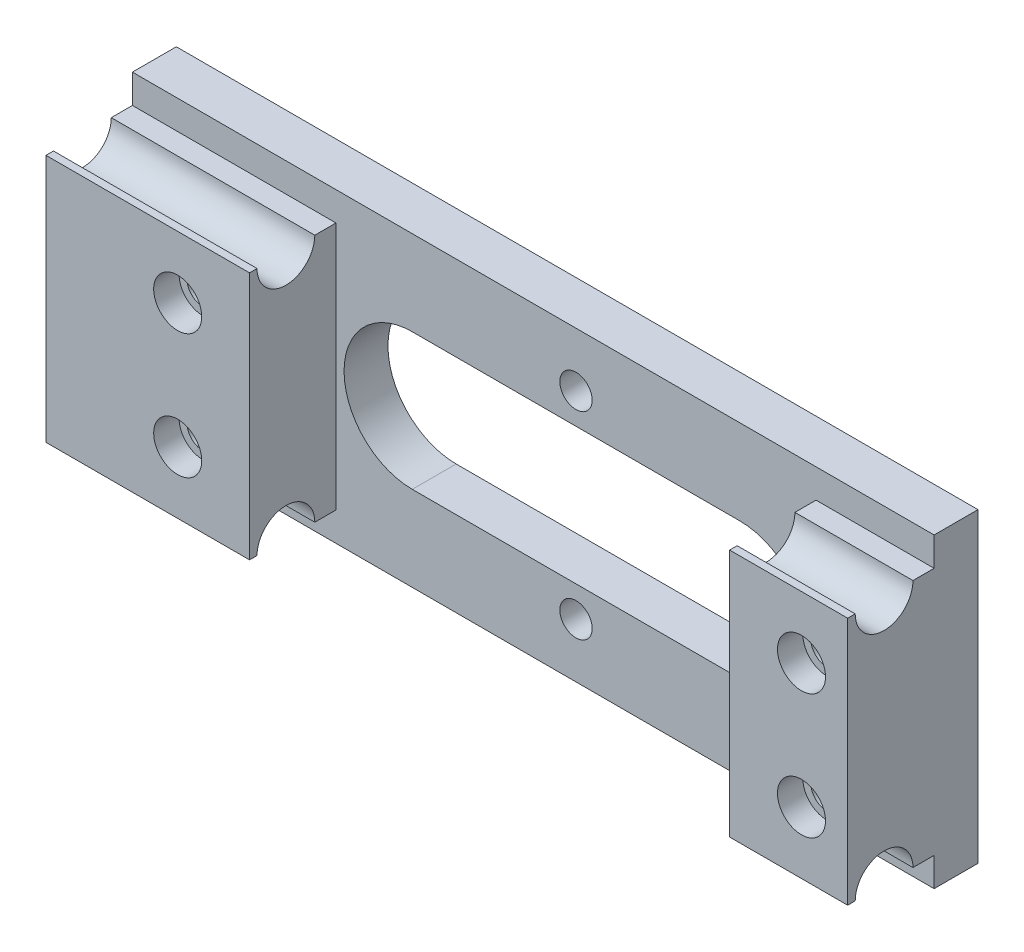
SolidWorks part; units mm, degrees
ref_plane "Front Plane" through (0, 0, 0) normal (0, 0, 1) x (1, 0, 0)
ref_plane "Top Plane" through (0, 0, 0) normal (0, 1, 0) x (1, 0, 0)
ref_plane "Right Plane" through (0, 0, 0) normal (1, 0, 0) x (0, 0, -1)
sketch "Sketch1" plane through (0, 0, 0) normal (0, 0, 1) x (1, 0, 0)
  line L1 (-22.0345, -8.4201) -> (22.0345, -8.4201)
  line L2 (-22.0345, -8.4201) -> (-22.0345, 8.4201)
  line L3 (-22.0345, 8.4201) -> (22.0345, 8.4201)
  line L4 (22.0345, -8.4201) -> (22.0345, 8.4201)
  line L5 (-22.0345, -8.4201) -> (22.0345, 8.4201) construction
  line L6 (-22.0345, 8.4201) -> (22.0345, -8.4201) construction
  point P0 (0, 0)
  dimension "D1" = 44.069
  dimension "D2" = 16.8402
extrude "Boss-Extrude1" add sketch "Sketch1" along normal blind 7.1628
sketch "Sketch2" plane through (0, 0, 7.1628) normal (0, 0, 1) x (1, 0, 0)
  line L0 (-22.0345, 0) -> (22.0345, 0) construction
  line L1 (-10.8458, 8.4201) -> (15.5448, 8.4201)
  line L2 (-10.8458, 8.4201) -> (-10.8458, -8.4201)
  line L3 (-10.8458, -8.4201) -> (15.5448, -8.4201)
  line L4 (15.5448, 8.4201) -> (15.5448, -8.4201)
  line L5 (-22.0345, 8.4201) -> (-22.0345, -8.4201) construction
  line L6 (22.0345, -8.4201) -> (22.0345, 8.4201) construction
  line L7 (-10.8458, 8.4201) -> (-22.0345, 0) construction
  line L8 (-22.0345, 0) -> (-10.8458, -8.4201) construction
  line L9 (2.3495, 8.4201) -> (2.3495, -8.4201) construction
  line L12 (22.0345, 8.4201) -> (-22.0345, 8.4201) construction
  dimension "D1" = 26.3906
  dimension "D2" = 24.384
extrude "Cut-Extrude1" cut sketch "Sketch2" against normal blind 4.75
sketch "Sketch4" plane through (0, 0, 7.1628) normal (0, 0, 1) x (1, 0, 0)
  line L0 (-10.8458, 8.4201) -> (-10.8458, -8.4201) construction
  line L1 (-22.0345, -8.4201) -> (-10.8458, -8.4201)
  line L2 (-22.0345, -8.4201) -> (-22.0345, -6.8326)
  line L3 (-22.0345, -6.8326) -> (-10.8458, -6.8326)
  line L4 (-10.8458, -8.4201) -> (-10.8458, -6.8326)
  line L5 (-22.0345, 0) -> (-10.8458, 0) construction
  line L6 (-22.0345, 8.4201) -> (-22.0345, -8.4201) construction
  line L7 (-10.8458, 8.4201) -> (-10.8458, -8.4201) construction
  line L8 (-10.8458, 8.4201) -> (-10.8458, 6.8326)
  line L9 (-22.0345, 6.8326) -> (-10.8458, 6.8326)
  line L10 (-22.0345, 8.4201) -> (-22.0345, 6.8326)
  line L11 (-22.0345, 8.4201) -> (-10.8458, 8.4201)
  line L12 (22.0345, -8.4201) -> (22.0345, 8.4201) construction
  line L13 (15.5448, -8.4201) -> (22.0345, -8.4201)
  line L14 (15.5448, -8.4201) -> (15.5448, -6.8326)
  line L15 (15.5448, -6.8326) -> (22.0345, -6.8326)
  line L16 (22.0345, -8.4201) -> (22.0345, -6.8326)
  line L17 (15.5448, 6.8326) -> (22.0345, 6.8326)
  line L18 (22.0345, 8.4201) -> (22.0345, 6.8326)
  line L19 (15.5448, 8.4201) -> (22.0345, 8.4201)
  line L20 (15.5448, 8.4201) -> (15.5448, 6.8326)
  dimension "D1" = 1.5875
extrude "Cut-Extrude9" cut sketch "Sketch4" against normal up to surface (4.75 mm away) up to face at (2.3495, 0, 2.4128)
sketch "Sketch5" plane through (-22.0345, 0, 0) normal (-1, 0, 0) x (0, 0, 1)
  line L1 (0, 0) -> (7.1628, 0) construction
  line L2 (0, 8.4201) -> (0, -8.4201) construction
  line L3 (7.1628, 6.8326) -> (7.1628, -6.8326) construction
  circle A0 centre (5.1628, -6.8326) radius 1.5875
  circle A1 centre (5.1628, 6.8326) radius 1.5875
  dimension "D1" = 3.175
  dimension "D2" = 2
extrude "Cut-Extrude10" cut sketch "Sketch5" against normal through all
sketch "Sketch6" plane through (0, 0, 7.1628) normal (0, 0, 1) x (1, 0, 0)
  line L0 (-22.0345, 0) -> (-10.8458, 0) construction
  line L1 (-22.0345, 6.8326) -> (-22.0345, -6.8326) construction
  line L2 (-10.8458, 6.8326) -> (-10.8458, -6.8326) construction
  circle A0 centre (-14.7955, 3.429) radius 0.889
  circle A1 centre (-14.7955, -3.429) radius 0.889
  circle A2 centre (19.4945, 3.429) radius 0.889
  circle A3 centre (19.4945, -3.429) radius 0.889
  dimension "D1" = 1.778
  dimension "D2" = 6.858
  dimension "D3" = 7.239
  dimension "D4" = 2
extrude "Cut-Extrude11" cut sketch "Sketch6" against normal through all
sketch "Sketch7" plane through (0, 0, 7.1628) normal (0, 0, 1) x (1, 0, 0)
  line L0 (-22.0345, 0) -> (-10.8458, 0) construction
  line L1 (-22.0345, 6.8326) -> (-22.0345, -6.8326) construction
  line L2 (-10.8458, 6.8326) -> (-10.8458, -6.8326) construction
  circle A0 centre (-14.7955, 3.429) radius 1.3208
  circle A1 centre (-14.7955, -3.429) radius 1.3208
  circle A2 centre (19.4945, 3.429) radius 1.3208
  circle A3 centre (19.4945, -3.429) radius 1.3208
  dimension "D1" = 2.6416
  dimension "D2" = 2
extrude "Cut-Extrude12" cut sketch "Sketch7" against normal blind 1.397
sketch "Sketch9" plane through (0, 0, 0) normal (0, 0, -1) x (-1, 0, 0)
  line L0 (22.0345, 8.4201) -> (22.0345, -8.4201) construction
  line L1 (-22.0345, 0) -> (22.0345, 0) construction
  line L2 (-22.0345, -8.4201) -> (-22.0345, 8.4201) construction
  circle A0 centre (-2.3495, 5.4356) radius 0.889
  circle A1 centre (-2.3495, -5.4356) radius 0.889
  dimension "D1" = 1.778
  dimension "D2" = 24.384
  dimension "D3" = 10.8712
extrude "Cut-Extrude13" cut sketch "Sketch9" against normal through all
sketch "Sketch10" plane through (0, 0, 0) normal (0, 0, -1) x (-1, 0, 0)
  line L0 (-22.0345, 0) -> (22.0345, 0) construction
  line L1 (-22.0345, -8.4201) -> (-22.0345, 8.4201) construction
  line L2 (22.0345, 8.4201) -> (22.0345, -8.4201) construction
  circle A0 centre (-2.3495, 5.4356) radius 1.1906
  circle A1 centre (-2.3495, -5.4356) radius 1.1906
  dimension "D1" = 2.3813
extrude "Cut-Extrude14" cut sketch "Sketch10" against normal blind 1
sketch "Sketch11" plane through (0, 0, 0) normal (0, 0, -1) x (-1, 0, 0)
  line L0 (-22.0345, 0) -> (22.0345, 0) construction
  line L1 (-22.0345, -8.4201) -> (-22.0345, 8.4201) construction
  line L2 (22.0345, 8.4201) -> (22.0345, -8.4201) construction
  line L3 (-2.3495, 5.4356) -> (-2.3495, -5.4356) construction
  line L4 (-11.3495, 0) -> (6.6505, 0) construction
  line L5 (-11.3495, 3.75) -> (6.6505, 3.75)
  line L6 (-11.3495, -3.75) -> (6.6505, -3.75)
  arc A0 (-11.3495, 3.75) -> (-11.3495, -3.75) centre (-11.3495, 0) ccw
  arc A1 (6.6505, -3.75) -> (6.6505, 3.75) centre (6.6505, 0) ccw
  point P12 (-2.3495, 0)
  dimension "D1" = 7.5
  dimension "D2" = 18
extrude "Cut-Extrude15" cut sketch "Sketch11" against normal through all
